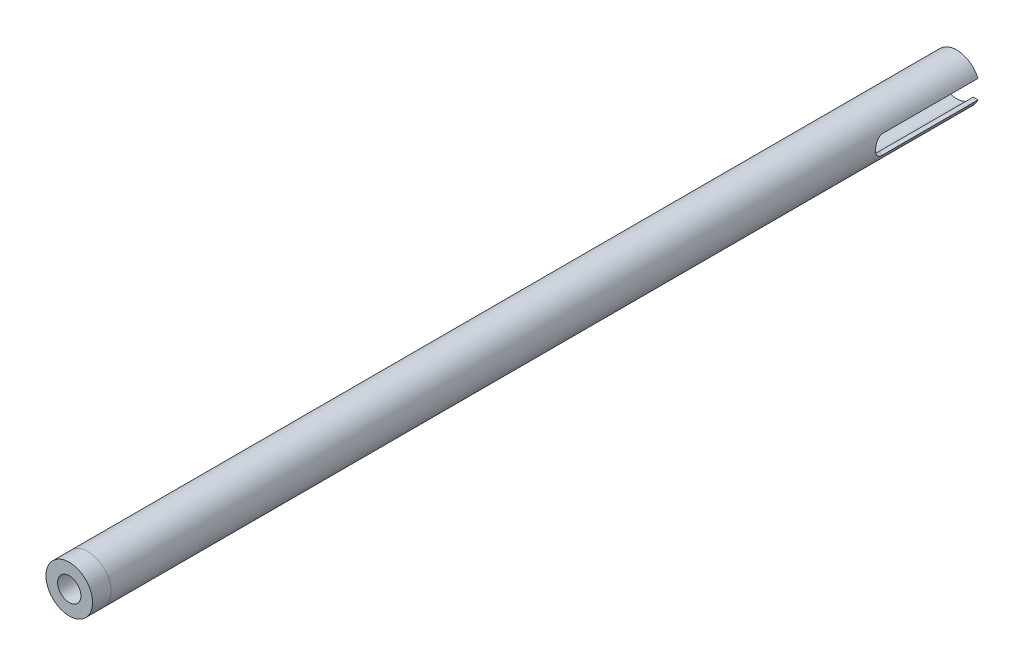
SolidWorks part; units mm, degrees
material "AISI 4130 Steel, normalized at 870C"
ref_plane "Front Plane" through (0, 0, 0) normal (0, 0, 1) x (1, 0, 0)
ref_plane "Top Plane" through (0, 0, 0) normal (0, 1, 0) x (1, 0, 0)
ref_plane "Right Plane" through (0, 0, 0) normal (1, 0, 0) x (0, 0, -1)
sketch "Axis" plane through (0, 0, 0) normal (0, 1, 0) x (1, 0, 0)
  line L0 (0, 0) -> (0, 302.3692) construction
  line L1 (0, 0) -> (0, -28.575) construction
  line L2 (0, 302.3692) -> (-7.9375, 302.3692) construction
  line L3 (0, 325.6526) -> (-31.298, 233.8452) construction
  dimension "D1" = 28.575
  dimension "D2" = 7.9375
sketch "Sketch1" plane through (0, 0, 0) normal (0, 0, 1) x (1, 0, 0)
  line L0 (-7.9375, 0) -> (7.9375, 0) construction
  line L1 (-7.2748, 3.175) -> (7.2748, 3.175)
  line L2 (-7.2748, -3.175) -> (7.2748, -3.175)
  circle A0 centre (0, 0) radius 7.9375
  circle A1 centre (0, 0) radius 6.4643
  circle A2 centre (0, 0) radius 3.9688
  dimension "D1" = 15.875
  dimension "D3" = 7.9375
  dimension "D2" = 1.4732
  dimension "D4" = 6.35
extrude "Threaded insert 1-1" add sketch "Sketch1" against normal blind 6.35 contours A2 L1 A1 | A1 L1 A0 | A2 L0 A1 L1 | A1 L0 A0 L1 | L0 A1 L2 A0 | L0 A2 L2 A1 | A2 L2 A1 | A1 L2 A0 | L0 A1 L2 A2 | L0 A0 L2 A1 | A0 L0 A1 L1 | A1 L0 A2 L1 region at (4.8156, 1.6537, 0) region at (4.8156, -1.6537, 0) region at (6.9501, 1.6161, 0) region at (6.9501, -1.6161, 0) region at (-4.8156, -1.6537, 0) region at (-4.8156, 1.6537, 0) region at (0, 4.6361, 0) region at (0, -4.6361, 0) region at (0, 6.6174, 0) region at (6.4528, -3.3281, 0) region at (-6.9501, -1.6161, 0) region at (-6.9501, 1.6161, 0)
extrude "Threaded insert 1-2" add sketch "Sketch1<3>" against normal blind 9.525 from surface contours A2 L1 A1 | A2 L0 A1 L1 | L0 A2 L2 A1 | A2 L2 A1 | L0 A1 L2 A2 | A1 L0 A2 L1 region at (4.8156, 1.6537, 0) region at (4.8156, -1.6537, 0) region at (-4.8156, -1.6537, 0) region at (-4.8156, 1.6537, 0) region at (0, 4.6361, 0) region at (0, -4.6361, 0) starting at face at (7.9375, 0, -6.35)
sketch "Sketch1<3>" plane through (0, 0, 0) normal (0, 0, 1) x (1, 0, 0) same geometry as "Sketch1"
extrude "A-arm tube" add sketch "Sketch1<4>" against normal up to vertex (302.3692 mm away) from surface separate body contours A1 L1 A0 | A1 L0 A0 L1 | L0 A1 L2 A0 | A1 L2 A0 | L0 A0 L2 A1 | A0 L0 A1 L1 region at (6.9501, 1.6161, 0) region at (6.9501, -1.6161, 0) region at (0, 6.6174, 0) region at (6.4528, -3.3281, 0) region at (-6.9501, -1.6161, 0) region at (-6.9501, 1.6161, 0) up to point (0, 0, -302.3692) starting at face at (6.4643, 0, -6.35)
sketch "Sketch1<4>" plane through (0, 0, 0) normal (0, 0, 1) x (1, 0, 0) same geometry as "Sketch1"
extrude "Apex slot" cut sketch "Sketch1<5>" along normal blind 35.56 from surface contours A0 L0 A1 L1 | L0 A0 L2 A1 | A1 L0 A0 L1 | L0 A1 L2 A0 region at (6.9501, 1.6161, 0) region at (6.9501, -1.6161, 0) region at (-6.9501, -1.6161, 0) region at (-6.9501, 1.6161, 0) starting at face at (6.4643, 0, -302.3692)
sketch "Sketch1<5>" plane through (0, 0, 0) normal (0, 0, 1) x (1, 0, 0) same geometry as "Sketch1"
fillet "Fillet1" radius 3.175 4 edges at (-6.4528, 3.175, -266.8092) (-6.4528, -3.175, -266.8092) (6.4528, -3.175, -266.8092) (6.4528, 3.175, -266.8092)
equation "\"tube diameter\"= 5 / 8"
equation "\"tube thickness\"= .058"
equation "\"apex thickness\"= .25"
equation "\"tube slot\"= 1.4"
equation "\"D1@Sketch1\"=\"tube diameter\""
equation "\"D2@Sketch1\"=\"tube thickness\""
equation "\"threaded insert hole\"= .3125"
equation "\"D3@Sketch1\"=\"threaded insert hole\""
equation "\"D4@Sketch1\"=\"apex thickness\""
equation "\"D1@Apex slot\" = \"tube slot\""
equation "\"D1@Fillet1\"=\"apex thickness\"/2"
equation "\"D2@Axis\"=\"tube diameter\"/2"
